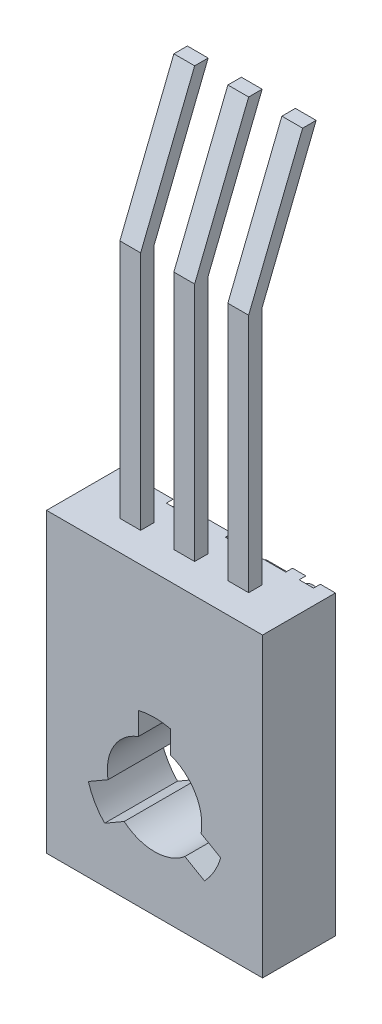
SolidWorks part; units mm, degrees
ref_plane "Front Plane" through (0, 0, 0) normal (0, 0, 1) x (1, 0, 0)
ref_plane "Top Plane" through (0, 0, 0) normal (0, 1, 0) x (1, 0, 0)
ref_plane "Right Plane" through (0, 0, 0) normal (1, 0, 0) x (0, 0, -1)
sketch "Sketch1" plane through (0, 0, 0) normal (0, 0, 1) x (1, 0, 0)
  line L1 (-4, 5.5) -> (4, 5.5)
  line L2 (-4, 5.5) -> (-4, -5.5)
  line L3 (-4, -5.5) -> (4, -5.5)
  line L4 (4, 5.5) -> (4, -5.5)
  line L5 (-4, 5.5) -> (4, -5.5) construction
  line L6 (-4, -5.5) -> (4, 5.5) construction
  circle A0 centre (0, -1.7) radius 2.555
  point P0 (0, 0)
  dimension "D3" = 5.11
  dimension "D1" = 11
  dimension "D2" = 8
  dimension "D4" = 3.8
extrude "Boss-Extrude1" add sketch "Sketch1" along normal mid plane 2.7
sketch "Sketch2" plane through (0, 5.5, 0) normal (0, 1, 0) x (1, 0, 0)
  line L0 (0, 0.8819) -> (0, -0.7814) construction
  line L1 (-0.385, 0.25) -> (0.385, 0.25)
  line L2 (-0.385, 0.25) -> (-0.385, -0.25)
  line L3 (-0.385, -0.25) -> (0.385, -0.25)
  line L4 (0.385, 0.25) -> (0.385, -0.25)
  line L5 (-0.385, 0.25) -> (0.385, -0.25) construction
  line L6 (-0.385, -0.25) -> (0.385, 0.25) construction
  line L7 (-2.385, 0.25) -> (-1.615, 0.25)
  line L8 (-2.385, 0.25) -> (-2.385, -0.25)
  line L9 (-2.385, -0.25) -> (-1.615, -0.25)
  line L10 (-1.615, 0.25) -> (-1.615, -0.25)
  line L11 (-2.385, 0.25) -> (-1.615, -0.25) construction
  line L12 (-2.385, -0.25) -> (-1.615, 0.25) construction
  line L13 (2.385, -0.25) -> (1.615, -0.25)
  line L14 (1.615, 0.25) -> (1.615, -0.25)
  line L15 (2.385, 0.25) -> (1.615, 0.25)
  line L16 (2.385, 0.25) -> (2.385, -0.25)
  point P0 (0, 0)
  point P7 (-2, 0)
  dimension "D1" = 0.5
  dimension "D2" = 0.77
  dimension "D3" = 0.77
  dimension "D4" = 0.5
  dimension "D5" = 2
extrude "Boss-Extrude2" add sketch "Sketch2" along normal blind 8.9
sketch "Sketch4" plane through (0, 0, 1.35) normal (0, 0, 1) x (1, 0, 0)
  line L0 (0, 0.8936) -> (0, -1.7) construction
  line L3 (-0.6, 0.8232) -> (-0.6, -0.0561)
  line L4 (0.6, 0.8232) -> (0.6, -0.0561)
  line L5 (2.4852, -2.442) -> (1.7237, -2.0023)
  line L6 (1.8852, -3.4812) -> (1.1237, -3.0416)
  line L7 (-1.8852, -3.4812) -> (-1.1237, -3.0416)
  line L8 (-2.4852, -2.442) -> (-1.7237, -2.0023)
  arc A0 (-1.1237, -3.0416) -> (1.1237, -3.0416) centre (0, -1.7) ccw
  arc A1 (-1.8852, -3.4812) -> (1.8852, -3.4812) centre (0, -1.7) ccw
  arc A2 (-0.6, -0.0561) -> (-1.7237, -2.0023) centre (0, -1.7) ccw
  arc A3 (-0.6, 0.8232) -> (-2.4852, -2.442) centre (0, -1.7) ccw
  arc A4 (1.7237, -2.0023) -> (0.6, -0.0561) centre (0, -1.7) ccw
  arc A5 (2.4852, -2.442) -> (0.6, 0.8232) centre (0, -1.7) ccw
  point P22 (0, -1.7)
  dimension "D1" = 3.5
  dimension "D2" = 0.6
  dimension "D3" = 3
extrude "Boss-Extrude3" add sketch "Sketch4" against normal up to surface (2.7 mm away) up to face at (0, 0, -1.35)
sketch "Sketch5" plane through (0, 0, -1.35) normal (0, 0, -1) x (-1, 0, 0)
  text T0 "TO126" font "Century Gothic" height in points 8
extrude "Cut-Extrude1" cut sketch "Sketch5" against normal blind 0.25
sketch "Sketch6" plane through (0, 14.4, 0) normal (0, 1, 0) x (1, 0, 0)
  line L0 (2.385, -0.25) -> (2.385, 0.25) construction
  line L1 (2.385, 0.25) -> (1.615, 0.25) construction
  line L2 (1.615, 0.25) -> (1.615, -0.25) construction
  line L3 (1.615, -0.25) -> (2.385, -0.25) construction
  line L4 (0.385, -0.25) -> (0.385, 0.25) construction
  line L5 (0.385, 0.25) -> (-0.385, 0.25) construction
  line L6 (-0.385, 0.25) -> (-0.385, -0.25) construction
  line L7 (-0.385, -0.25) -> (0.385, -0.25) construction
  line L8 (-1.615, -0.25) -> (-1.615, 0.25) construction
  line L9 (-1.615, 0.25) -> (-2.385, 0.25) construction
  line L10 (-2.385, 0.25) -> (-2.385, -0.25) construction
  line L11 (-2.385, -0.25) -> (-1.615, -0.25) construction
  line L12 (2.385, -0.25) -> (2.385, 0.25)
  line L13 (2.385, 0.25) -> (1.615, 0.25)
  line L14 (1.615, 0.25) -> (1.615, -0.25)
  line L15 (1.615, -0.25) -> (2.385, -0.25)
  line L16 (0.385, -0.25) -> (0.385, 0.25)
  line L17 (0.385, 0.25) -> (-0.385, 0.25)
  line L18 (-0.385, 0.25) -> (-0.385, -0.25)
  line L19 (-0.385, -0.25) -> (0.385, -0.25)
  line L20 (-1.615, -0.25) -> (-1.615, 0.25)
  line L21 (-1.615, 0.25) -> (-2.385, 0.25)
  line L22 (-2.385, 0.25) -> (-2.385, -0.25)
  line L23 (-2.385, -0.25) -> (-1.615, -0.25)
sketch "Sketch7" plane through (0, 0, 0) normal (1, 0, 0) x (0, 0, -1)
  line L0 (0, 14.4) -> (2, 19.4)
  line L1 (0.25, 14.4) -> (-0.25, 14.4) construction
  line L3 (0, 14.4) -> (0, 19.4) construction
  dimension "D1" = 2
  dimension "D2" = 5
sweep "Sweep1" add profiles "Sketch6" path "Sketch7"
